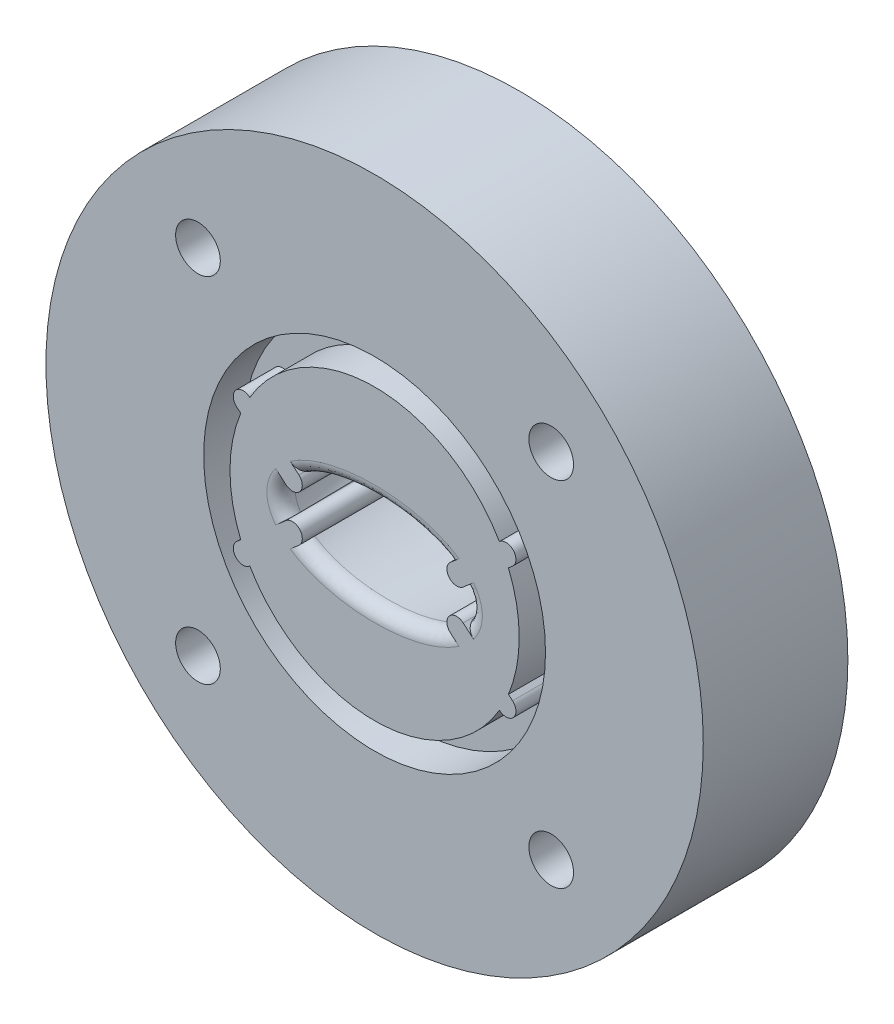
SolidWorks part; units mm, degrees
ref_plane "Plan de face" through (0, 0, 0) normal (0, 0, 1) x (1, 0, 0)
ref_plane "Plan de dessus" through (0, 0, 0) normal (0, 1, 0) x (1, 0, 0)
ref_plane "Plan de droite" through (0, 0, 0) normal (1, 0, 0) x (0, 0, -1)
sketch "Esquisse1" plane through (0, 0, 0) normal (0, 0, 1) x (1, 0, 0)
  circle A0 centre (0, 0) radius 25
  circle A1 centre (-13.435, 13.435) radius 1.7
  circle A2 centre (13.435, 13.435) radius 1.7
  circle A3 centre (13.435, -13.435) radius 1.7
  circle A4 centre (-13.435, -13.435) radius 1.7
  point P19 (0, 0)
  dimension "D1" = 50
  dimension "D5" = 19
  dimension "D6" = 3.4
  dimension "D4" = 4
extrude "Boss.-Extru.1" add sketch "Esquisse1" along normal blind 11
sketch "Esquisse4" plane through (0, 0, 11) normal (0, 0, 1) x (1, 0, 0)
  ellipse E0 centre (0, 0) end of major axis (-7, 0) minor radius 3.5
  dimension "D1" = 7
  dimension "D2" = 14
sketch "Esquisse5" plane through (0, 0, 0) normal (0, 0, -1) x (-1, 0, 0)
  ellipse E0 centre (0, 0) end of major axis (9, 0) minor radius 4
  dimension "D1" = 8
  dimension "D2" = 18
loft "Enlèvement de matière-Lissage1" cut profiles "Esquisse5", "Esquisse4" connector at (0.0922, -3.9998, 0) connector at (-0.1656, -3.499, 11)
sketch "Esquisse2" plane through (0, 0, 11) normal (0, 0, 1) x (1, 0, 0)
  circle A0 centre (0, 0) radius 13
  circle A1 centre (0, 0) radius 11
  dimension "D1" = 22
  dimension "D2" = 26
extrude "Enlèv. mat.-Extru.1" cut sketch "Esquisse2" against normal blind 3
ref_axis "Axe1" through (0, 0, 0.0524) along (0, 0, 1)
ref_plane "Plan1" through (0, 0, 0) normal (1, 0, 0) x (0, 0, -1)
fillet "Congé1" radius 1 1 edges at (-7, 0, 11)
sketch "Esquisse6" plane through (0, 0, 0) normal (0, 0, -1) x (-1, 0, 0)
  circle A0 centre (0, 0) radius 11
  dimension "D1" = 22
extrude "Enlèv. mat.-Extru.2" cut sketch "Esquisse6" against normal blind 3
fillet "Congé2" radius 0.5 1 edges at (-11, 0, 3)
fillet "Congé3" radius 0.5 1 edges at (0.2153, 3.8619, 3)
sketch "Esquisse8" plane through (0, 0, 11) normal (0, 0, 1) x (1, 0, 0)
  line L0 (-6.5, 2) -> (6.5, 2) construction
  line L1 (6.5, 2) -> (6.5, -2) construction
  line L2 (6.5, -2) -> (-6.5, -2) construction
  line L3 (-6.5, 2) -> (-6.5, -2) construction
  line L4 (-6.25, 1.75) -> (-6.25, 2) construction
  line L5 (-6.25, 1.75) -> (-6.5, 1.75) construction
  line L6 (-6.25, -1.75) -> (-6.5, -1.75) construction
  line L7 (-6.25, -1.75) -> (-6.25, -2) construction
  line L8 (6.25, 1.75) -> (6.25, 2) construction
  line L9 (6.25, 1.75) -> (6.5, 1.75) construction
  line L10 (6.25, -1.75) -> (6.5, -1.75) construction
  line L11 (6.25, -1.75) -> (6.25, -2) construction
  line L12 (6.5, 0) -> (-6.5, 0) construction
  circle A0 centre (-6.25, 1.75) radius 0.25
  circle A1 centre (-6.25, -1.75) radius 0.25
  circle A2 centre (6.25, 1.75) radius 0.25
  circle A3 centre (6.25, -1.75) radius 0.25
  point P21 (0, 0)
extrude "Boss.-Extru.4" add sketch "Esquisse8" against normal blind 10
sketch "Esquisse9" plane through (0, 0, 1) normal (0, 0, -1) x (-1, 0, 0)
sketch "Esquisse10" plane through (0, 0, 11) normal (0, 0, 1) x (1, 0, 0)
  line L0 (-10, 0) -> (10, 0) construction
  line L1 (10, 0) -> (10, 5) construction
  line L2 (10, 5) -> (-10, 5) construction
  line L3 (-10, 5) -> (-10, 0) construction
  line L4 (6.5, -2) -> (-6.5, -2) construction
  line L5 (-6.5, 2) -> (6.5, 2) construction
  line L6 (6.5, 2) -> (6.5, -2) construction
  line L7 (6.5, 0) -> (-6.5, 0) construction
  line L8 (9.2495, -0.5365) -> (9.2495, 3.4635) construction
  line L9 (10, 0) -> (10, -5) construction
  line L10 (10, -5) -> (-10, -5) construction
  line L11 (-10, -5) -> (-10, 0) construction
  line L12 (-6.25, -1.75) -> (-10, -5) construction
  line L13 (-5.7588, -2.3168) -> (-9.5088, -5.5668)
  line L14 (-6.7412, -1.1832) -> (-10.4912, -4.4332)
  line L15 (-6.25, 1.75) -> (-10, 5) construction
  line L16 (-6.7412, 1.1832) -> (-10.4912, 4.4332)
  line L17 (-5.7588, 2.3168) -> (-9.5088, 5.5668)
  line L18 (10, -5) -> (6.25, -1.75) construction
  line L19 (9.5088, -5.5668) -> (5.7588, -2.3168)
  line L20 (10.4912, -4.4332) -> (6.7412, -1.1832)
  line L21 (10, 5) -> (6.25, 1.75) construction
  line L22 (10.4912, 4.4332) -> (6.7412, 1.1832)
  line L23 (9.5088, 5.5668) -> (5.7588, 2.3168)
  arc A0 (-5.7588, -2.3168) -> (-6.7412, -1.1832) centre (-6.25, -1.75) ccw
  arc A1 (-10.4912, -4.4332) -> (-9.5088, -5.5668) centre (-10, -5) ccw
  arc A2 (-6.7412, 1.1832) -> (-5.7588, 2.3168) centre (-6.25, 1.75) ccw
  arc A3 (-9.5088, 5.5668) -> (-10.4912, 4.4332) centre (-10, 5) ccw
  arc A4 (9.5088, -5.5668) -> (10.4912, -4.4332) centre (10, -5) ccw
  arc A5 (6.7412, -1.1832) -> (5.7588, -2.3168) centre (6.25, -1.75) ccw
  arc A6 (10.4912, 4.4332) -> (9.5088, 5.5668) centre (10, 5) ccw
  arc A7 (5.7588, 2.3168) -> (6.7412, 1.1832) centre (6.25, 1.75) ccw
  point P12 (0, 0)
  point P18 (-8.125, -3.375)
  point P24 (-8.125, 3.375)
  point P31 (8.125, -3.375)
  point P38 (8.125, 3.375)
extrude "Boss.-Extru.6" add sketch "Esquisse10" against normal blind 10
equation "\"9.5.00mm\"=6"
